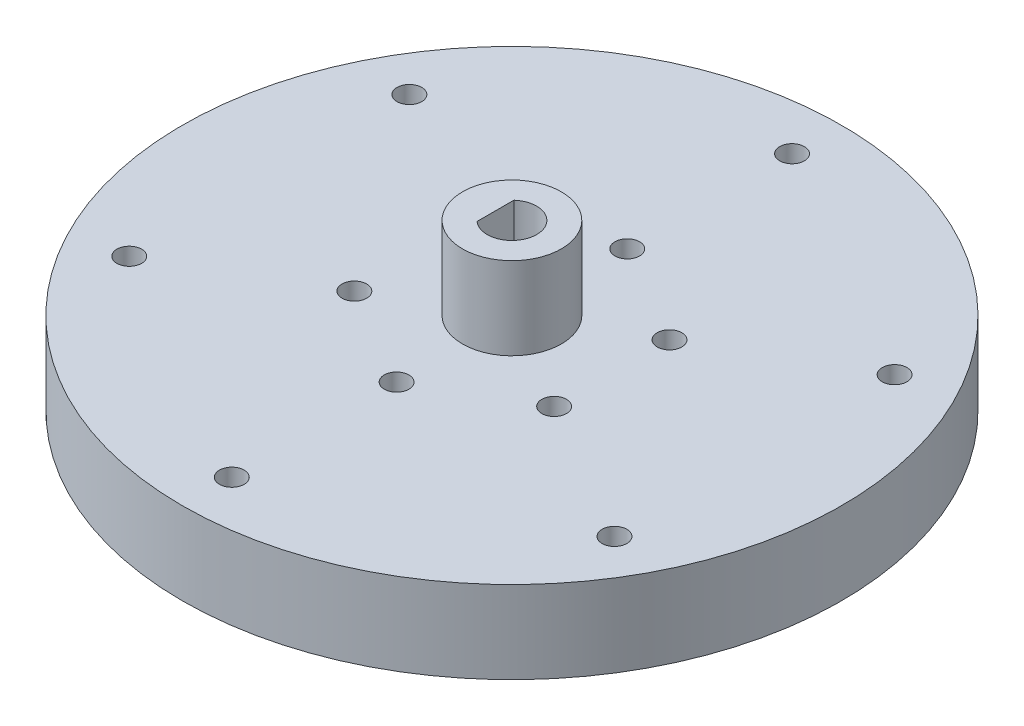
SolidWorks part; units mm, degrees
ref_plane "前视基准面" through (0, 0, 0) normal (0, 0, 1) x (1, 0, 0)
ref_plane "上视基准面" through (0, 0, 0) normal (0, 1, 0) x (1, 0, 0)
ref_plane "右视基准面" through (0, 0, 0) normal (1, 0, 0) x (0, 0, -1)
other "Configuration Table"
sketch "草图1" plane through (0, 0, 0) normal (0, 1, 0) x (1, 0, 0)
  line L0 (-1, 1.118) -> (-1, -1.118)
  circle A7 centre (0, 0) radius 20
  circle A8 centre (0, 0) radius 1.5
  circle A9 centre (0, 0) radius 3
  point P0 (0, 0)
  dimension "D3" = 6
  dimension "D4" = 40
  dimension "D1" = 3
  dimension "D2" = 1
extrude "凸台-拉伸1" add sketch "草图1" along normal blind 5 contours A7
extrude "凸台-拉伸2" add sketch "草图1<7>" along normal blind 10 contours A9 A8 | L0 A8 region at (-1.2032, 0, 0) region at (-2.9151, 0, 0)
sketch "草图1<7>" plane through (0, 0, 0) normal (0, 1, 0) x (1, 0, 0) same geometry as "草图1"
sketch "草图2" plane through (0, 0, 0) normal (0, -1, 0) x (1, 0, 0)
  circle A0 centre (0, -7) radius 0.75
  circle A1 centre (0, -17) radius 0.75
  point P2 (0, -7.8309)
  point P3 (0, 0)
  dimension "D1" = 1.5
  dimension "D2" = 10
  dimension "D3" = 7
extrude "切除-拉伸1" cut sketch "草图2" against normal through all
pattern_circular "阵列(圆周)1" count 6 over 360 about axis through (0, 5, 0) along (0, -1, 0) of "切除-拉伸1"
